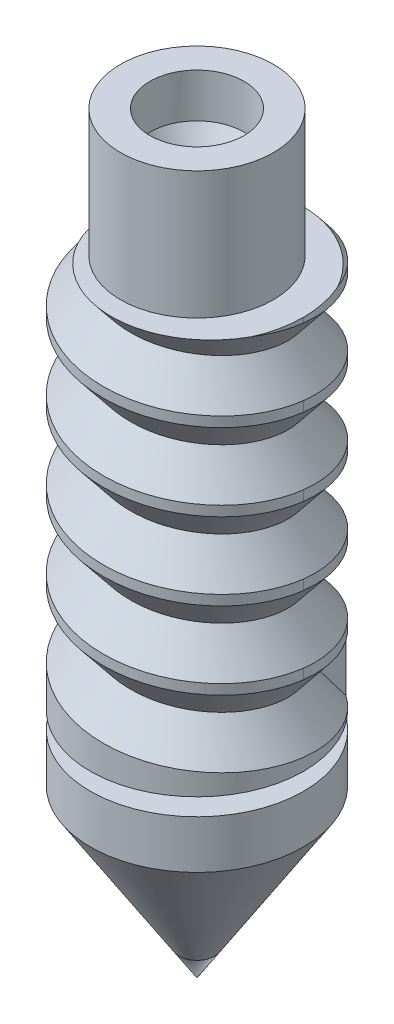
SolidWorks part; units mm, degrees
ref_plane "Front Plane" through (0, 0, 0) normal (0, 0, 1) x (1, 0, 0)
ref_plane "Top Plane" through (0, 0, 0) normal (0, 1, 0) x (1, 0, 0)
ref_plane "Right Plane" through (0, 0, 0) normal (1, 0, 0) x (0, 0, -1)
sketch "Sketch1" plane through (0, 0, 0) normal (0, 0, 1) x (1, 0, 0)
  line L0 (0, 0) -> (2.6971, 4.219)
  line L1 (1.9351, 19.05) -> (1.9351, 15.8253)
  line L2 (1.9351, 19.05) -> (1.1906, 19.05)
  line L3 (1.1906, 19.05) -> (1.1906, 17.9372)
  line L4 (0, 0) -> (0, 15.875)
  line L5 (0, 15.875) -> (1.1906, 17.9372)
  line L6 (1.9351, 15.8253) -> (2.6971, 15.8253)
  line L7 (2.6971, 15.8253) -> (2.6971, 5.8757)
  line L8 (2.6971, 5.8757) -> (1.9351, 5.8757)
  line L9 (1.9351, 5.8757) -> (1.9351, 5.4385)
  line L10 (1.9351, 5.4385) -> (2.6971, 5.4385)
  line L11 (2.6971, 5.4385) -> (2.6971, 4.219)
  dimension "D2" = 3.175
  dimension "D3" = 2.6971
  dimension "D4" = 0.762
  dimension "D5" = 0.762
  dimension "D6" = 19.05
revolve "Revolve1" add sketch "Sketch1" angle 360 about L4
sketch "Sketch2" plane through (0, 15.8253, 0) normal (0, 1, 0) x (1, 0, 0)
  circle A0 centre (0, 0) radius 2.6971
curve "Helix/Spiral1" pitch 1.9538 height 10.5508 radius 2.6971 left hand yes centre (0, 15.8253, 0) axis (0, -1, 0) start towards (0, 0, 1)
sketch "Sketch4" plane through (0, 0, 0) normal (0, 0, 1) x (1, 0, 0)
  line L1 (-2.013, 15.8253) -> (-2.6971, 14.9753)
  line L2 (-2.6971, 15.8253) -> (-2.6971, 5.8757) construction
  line L3 (-2.6971, 14.9753) -> (-2.6971, 16.6752)
  line L5 (2.6971, 15.8253) -> (-2.6971, 15.8253) construction
  line L6 (-2.013, 15.8253) -> (-2.6971, 16.6752)
sweep "Cut-Sweep9" cut profiles "Sketch4" path "Helix/Spiral1" align with end faces yes
